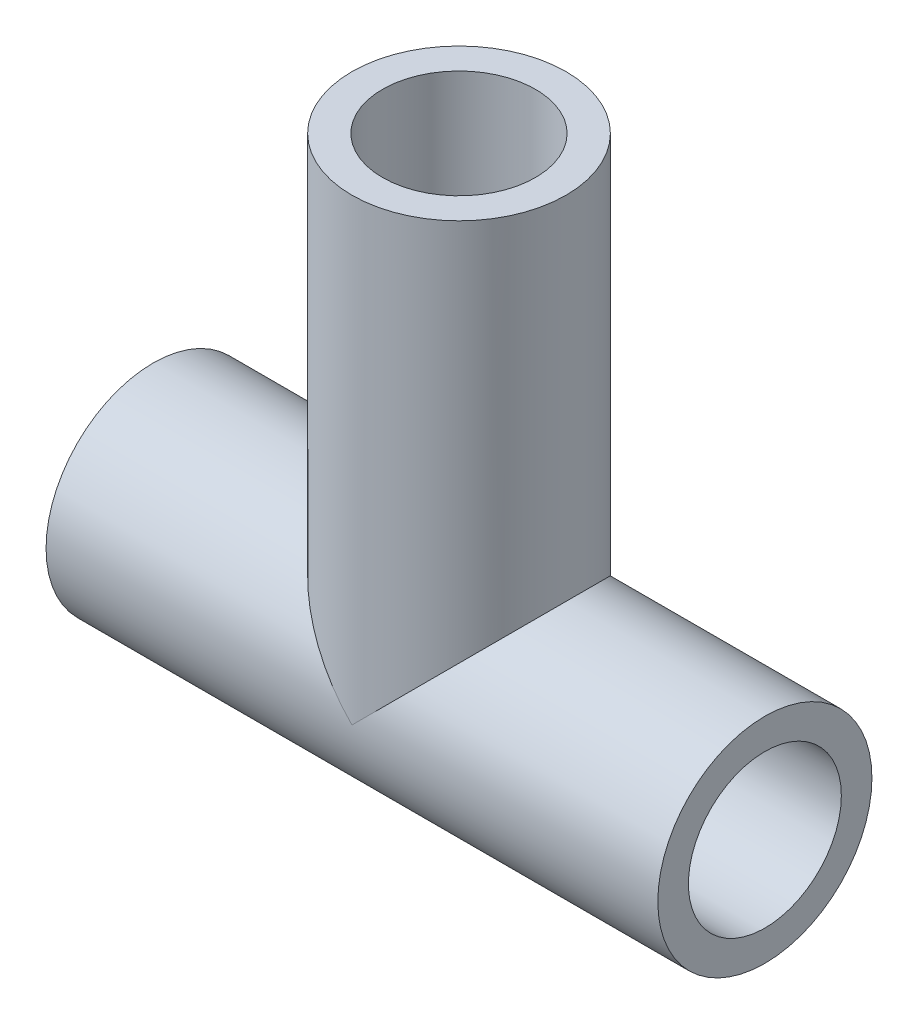
SolidWorks part; units mm, degrees
ref_plane "Front Plane" through (0, 0, 0) normal (0, 0, 1) x (1, 0, 0)
ref_plane "Top Plane" through (0, 0, 0) normal (0, 1, 0) x (1, 0, 0)
ref_plane "Right Plane" through (0, 0, 0) normal (1, 0, 0) x (0, 0, -1)
sketch "Sketch1" plane through (0, 0, 0) normal (1, 0, 0) x (0, 0, -1)
  circle A0 centre (0, 0) radius 4.445
  dimension "D2" = 8.89
extrude "Boss-Extrude1" add sketch "Sketch1" along normal blind 25.4
sketch "Sketch2" plane through (0, 0, 0) normal (0, 1, 0) x (1, 0, 0)
  circle A1 centre (12.7, 0) radius 4.445
  dimension "D3" = 8.89
  dimension "D1" = 12.7
extrude "Boss-Extrude2" add sketch "Sketch2" along normal blind 19.05
sketch "Sketch3" plane through (25.4, 0, 0) normal (1, 0, 0) x (0, 0, -1)
  circle A0 centre (0, 0) radius 3.175
  dimension "D1" = 6.35
extrude "Cut-Extrude1" cut sketch "Sketch3" against normal through all
sketch "Sketch4" plane through (0, 19.05, 0) normal (0, 1, 0) x (1, 0, 0)
  circle A0 centre (12.7, 0) radius 3.175
  dimension "D1" = 6.35
extrude "Cut-Extrude2" cut sketch "Sketch4" against normal up to next
